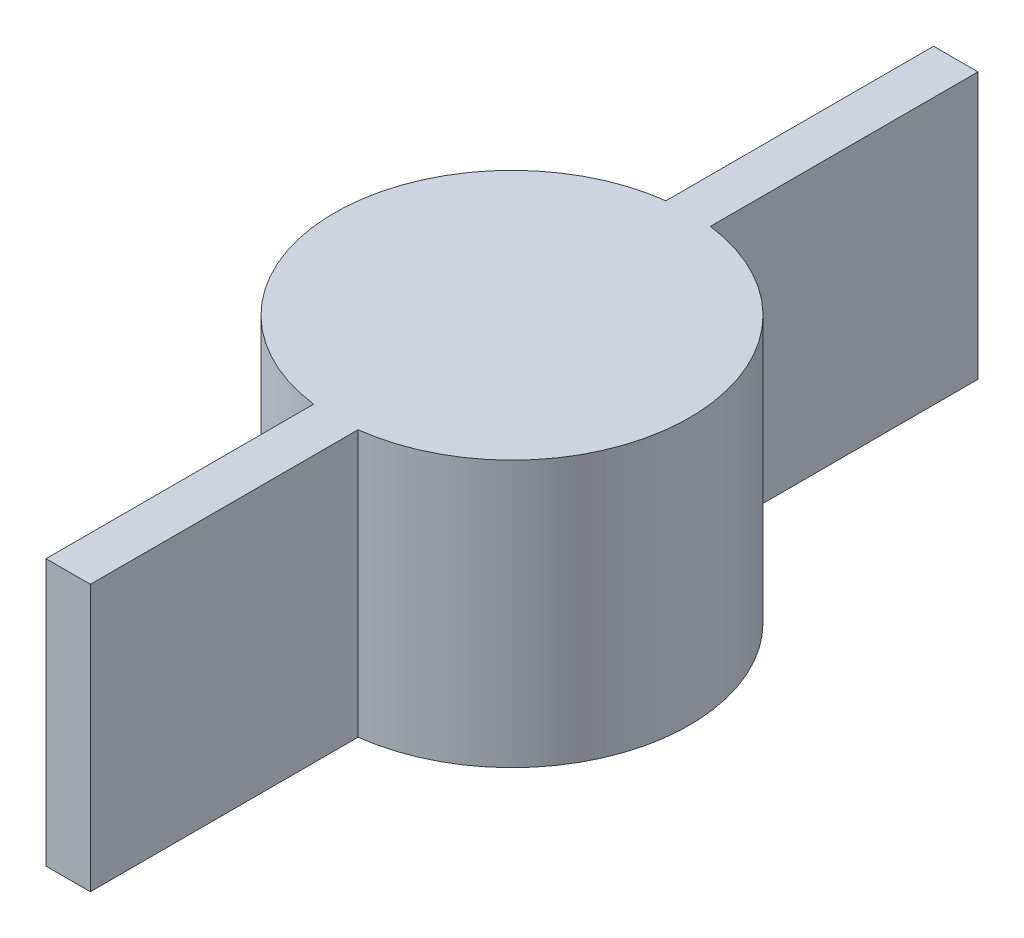
SolidWorks part; units mm, degrees
ref_plane "Front" through (0, 0, 0) normal (0, 0, 1) x (1, 0, 0)
ref_plane "Top" through (0, 0, 0) normal (0, 1, 0) x (1, 0, 0)
ref_plane "Right" through (0, 0, 0) normal (1, 0, 0) x (0, 0, -1)
sketch "草图1" plane through (0, 0, 0) normal (0, 1, 0) x (1, 0, 0)
  line L0 (0, 58.1692) -> (0, -55.7643) construction
  line L1 (-43.5893, 0) -> (40.8838, 0) construction
  line L2 (-2.5, 50) -> (-2.5, 19.8431)
  line L3 (-2.5, -50) -> (2.5, -50)
  line L4 (2.5, -50) -> (2.5, -19.8431)
  line L5 (2.5, 50) -> (-2.5, 50)
  line L6 (-2.5, -19.8431) -> (-2.5, -50)
  line L7 (2.5, 19.8431) -> (2.5, 50)
  arc A0 (-2.5, 19.8431) -> (-2.5, -19.8431) centre (0, 0) ccw
  arc A1 (2.5, -19.8431) -> (2.5, 19.8431) centre (0, 0) ccw
  dimension "D1" = 20
  dimension "D2" = 5
  dimension "D3" = 100
extrude "凸台-拉伸1" add sketch "草图1" along normal blind 30
ref_axis "转轴中心轴" through (0, 50, 0) along (0, -1, 0)
sketch "草图2" plane through (0, 30, 0) normal (0, 1, 0) x (1, 0, 0)
  line L1 (-7.5, -7.5) -> (7.5, -7.5)
  line L2 (-7.5, -7.5) -> (-7.5, 7.5)
  line L3 (-7.5, 7.5) -> (7.5, 7.5)
  line L4 (7.5, -7.5) -> (7.5, 7.5)
  line L5 (-7.5, -7.5) -> (7.5, 7.5) construction
  line L6 (-7.5, 7.5) -> (7.5, -7.5) construction
  point P0 (0, 0)
  dimension "D1" = 15
  dimension "D2" = 15
extrude "凸台-拉伸2" [suppressed] add sketch "草图2" along normal blind 10
